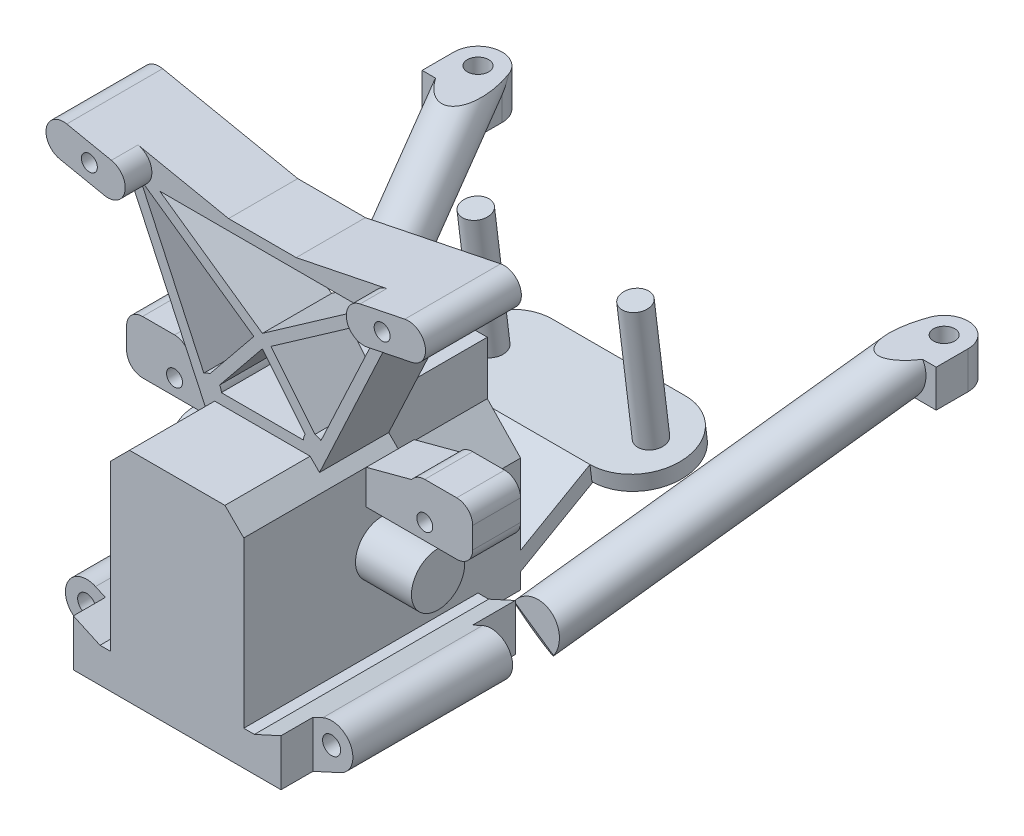
SolidWorks part; units mm, degrees
ref_plane "Front Plane" through (0, 0, 0) normal (0, 0, 1) x (1, 0, 0)
ref_plane "Top Plane" through (0, 0, 0) normal (0, 1, 0) x (1, 0, 0)
ref_plane "Right Plane" through (0, 0, 0) normal (1, 0, 0) x (0, 0, -1)
sketch "Sketch1" plane through (0, 0, 0) normal (1, 0, 0) x (0, 0, -1)
  circle A0 centre (0, 0) radius 5
  dimension "D1" = 10
extrude "Driveline Axis" add sketch "Sketch1" along normal mid plane 46 contours A0
sketch "Sketch2" plane through (0, 0, 0) normal (0, 0, 1) x (1, 0, 0)
  line L0 (-12.5, -20) -> (-12.5, 14.4645)
  line L1 (-12.5, 14.4645) -> (-8.9645, 18)
  line L2 (-8.9645, 18) -> (8.9645, 18)
  line L3 (8.9645, 18) -> (12.5, 14.4645)
  line L4 (12.5, 14.4645) -> (12.5, -20)
  line L5 (12.5, -20) -> (-12.5, -20)
  dimension "D1" = 20
  dimension "D2" = 18
  dimension "D3" = 5
  dimension "D4" = 5
  dimension "D5" = 25
  dimension "D6" = 12.5
extrude "Dummy Boss" add sketch "Sketch2" along normal mid plane 52
ref_plane "Pin Base Plane" through (0, 0, -18) normal (0, 0, -1) x (-1, 0, 0)
sketch "Sketch3" plane through (0, 0, -18) normal (0, 0, -1) x (-1, 0, 0)
  line L0 (-19.5, -23) -> (19.5, -23)
  line L1 (19.5, -23) -> (24.6641, -20.6374)
  line L2 (21.3359, -13.3626) -> (14.5, -16.49)
  line L3 (14.5, -16.49) -> (12.5, -16.49)
  line L4 (12.5, 14.4645) -> (12.5, -20) construction
  line L5 (12.5, -16.49) -> (12.5, -20)
  line L6 (12.5, -20) -> (-12.5, -20)
  line L7 (12.5, -20) -> (-12.5, -20) construction
  line L8 (0, -20) -> (0, -23) construction
  line L9 (-12.5, -16.49) -> (-12.5, -20)
  line L10 (-14.5, -16.49) -> (-12.5, -16.49)
  line L11 (-21.3359, -13.3626) -> (-14.5, -16.49)
  line L12 (-19.5, -23) -> (-24.6641, -20.6374)
  arc A0 (24.6641, -20.6374) -> (21.3359, -13.3626) centre (23, -17) ccw
  arc A1 (-24.6641, -20.6374) -> (-21.3359, -13.3626) centre (-23, -17) cw
  dimension "D3" = 4
  dimension "D1" = 17
  dimension "D2" = 23
  dimension "D4" = 3
  dimension "D5" = 2
  dimension "D6" = 7
extrude "Pin Base" add sketch "Sketch3" against normal up to surface (44 mm away) up to face at (0, 4.1548, 26)
hole_wizard "Pin Holes" positions "Sketch5" profile "Sketch7" hole size "M3" standard "ANSI Metric" end condition through all
sketch "Sketch5" plane through (0, 0, -18) normal (0, 0, -1) x (-1, 0, 0)
  arc A0 (24.6641, -20.6374) -> (21.3359, -13.3626) centre (23, -17) ccw construction
  arc A1 (-21.3359, -13.3626) -> (-24.6641, -20.6374) centre (-23, -17) ccw construction
  point P0 (-23, -17)
  point P2 (23, -17)
sketch "Sketch7" plane through (23, -17, -18) normal (1, 0, 0) x (0, 1, 0)
  line L0 (0, 0) -> (0, 44)
  line L1 (0, 44) -> (1.7, 44)
  line L2 (1.7, 44) -> (1.7, 0)
  line L5 (1.7, 0) -> (0, 0)
  line L11 (0, -6.35) -> (0, 107.95) construction
  dimension "Thru Hole Dia." = 3.4
  dimension "Thru Hole Depth" = 44
sketch "Sketch8" plane through (0, 0, 0) normal (0, 0, 1) x (1, 0, 0)
  line L0 (-10.7322, 16.2322) -> (-24.6615, 46.1036)
  line L1 (-8.9645, 18) -> (-12.5, 14.4645) construction
  line L2 (-24.6615, 46.1036) -> (-33.049, 47.8157)
  line L3 (-31.749, 54.1843) -> (-6.351, 49)
  line L4 (9.8662, 21.9942) -> (1.6121, 32.1873)
  line L5 (-6.351, 49) -> (6.351, 49)
  line L6 (0, 49) -> (0, 18) construction
  line L7 (8.9645, 18) -> (-8.9645, 18) construction
  line L8 (8.9645, 18) -> (-8.9645, 18)
  line L9 (-8.9645, 18) -> (-10.7322, 16.2322)
  line L10 (7.7145, 20) -> (-7.7145, 20)
  line L11 (-10.9977, 21.534) -> (-22.924, 47.11)
  line L12 (-8.032, 21.0813) -> (0, 31)
  line L13 (-9.8662, 21.9942) -> (-1.6121, 32.1873)
  line L14 (-1.6121, 32.1873) -> (-22.924, 47.11)
  line L15 (-19.28, 47) -> (0, 33.5)
  line L16 (8.032, 21.0813) -> (0, 31)
  line L17 (-19.28, 47) -> (19.28, 47)
  line L18 (8.9645, 18) -> (10.7322, 16.2322)
  line L19 (19.28, 47) -> (0, 33.5)
  line L20 (1.6121, 32.1873) -> (22.924, 47.11)
  line L21 (10.9977, 21.534) -> (22.924, 47.11)
  line L22 (10.7322, 16.2322) -> (24.6615, 46.1036)
  line L23 (24.6615, 46.1036) -> (33.049, 47.8157)
  line L24 (31.749, 54.1843) -> (6.351, 49)
  arc A0 (-33.049, 47.8157) -> (-31.749, 54.1843) centre (-32.399, 51) cw
  arc A1 (-7.7145, 20) -> (-8.032, 21.0813) centre (-9.7145, 20) ccw
  arc A2 (-9.8662, 21.9942) -> (-10.9977, 21.534) centre (-9.7145, 20) ccw
  circle A4 centre (-27.5, 50) radius 1.5
  arc A6 (9.8662, 21.9942) -> (10.9977, 21.534) centre (9.7145, 20) cw
  arc A7 (7.7145, 20) -> (8.032, 21.0813) centre (9.7145, 20) cw
  arc A8 (33.049, 47.8157) -> (31.749, 54.1843) centre (32.399, 51) ccw
  circle A10 centre (27.5, 50) radius 1.5
  point P32 (-5.7392, 27.0907)
  point P50 (0, 20)
  point P52 (0, 47)
  dimension "D1" = 2
  dimension "D6" = 2
  dimension "D10" = 3.25
  dimension "D11" = 55
  dimension "D12" = 29
  dimension "D13" = 3
  dimension "D2" = 2
  dimension "D3" = 2
  dimension "D4" = 2
  dimension "D5" = 2
  dimension "D7" = 0.75
  dimension "D8" = 2
  dimension "D9" = 50
  dimension "D14" = 5
  dimension "D15" = 86
  dimension "D16" = 3.25
  dimension "D17" = 64
  dimension "D18" = 11
  dimension "D19" = 51
  dimension "D20" = 33
  dimension "D24" = 2.5
extrude "Uprights" add sketch "Sketch8" along normal blind 10 and the other way blind 3 contours A2 L13 L14 L11 | L17 L6 L19 | L6 L17 L15 | L4 A6 L21 L20 | L16 L6 L10 A7 | L6 L12 A1 L10 | A4 | A10 | L22 L23 A8 L24 L5 L3 A0 L2 L0 L9 L8 L18 region at (-2.8929, 23.7148, 0) region at (2.8929, 23.7148, 0) region at (-6.4267, 42.5, 0) region at (6.4267, 42.5, 0) region at (11.7554, 33.4425, 0) region at (-11.7554, 33.4425, 0) region at (-27.5, 50, 0) region at (27.5, 50, 0)
sketch "Sketch9" plane through (0, 0, 10) normal (0, 0, 1) x (1, 0, 0)
  line L0 (-24.6615, 46.1036) -> (-33.049, 47.8157)
  line L1 (-31.749, 54.1843) -> (-23.3615, 52.4722)
  line L2 (-31.749, 54.1843) -> (-6.351, 49) construction
  line L3 (23.3615, 52.4722) -> (31.749, 54.1843)
  line L4 (31.749, 54.1843) -> (6.351, 49) construction
  line L5 (33.049, 47.8157) -> (24.6615, 46.1036)
  circle A0 centre (-27.5, 50) radius 1.5
  circle A1 centre (27.5, 50) radius 1.5
  circle A2 centre (27.5, 50) radius 1.5 construction
  circle A3 centre (-27.5, 50) radius 1.5 construction
  arc A4 (-33.049, 47.8157) -> (-31.749, 54.1843) centre (-32.399, 51) cw
  arc A5 (-31.749, 54.1843) -> (-33.049, 47.8157) centre (-32.399, 51) ccw construction
  arc A6 (-23.3615, 52.4722) -> (-24.6615, 46.1036) centre (-24.0115, 49.2879) cw
  arc A7 (31.749, 54.1843) -> (33.049, 47.8157) centre (32.399, 51) cw
  arc A8 (24.6615, 46.1036) -> (23.3615, 52.4722) centre (24.0115, 49.2879) cw
extrude "Shock Mount" add sketch "Sketch9" along normal blind 5 and the other way blind 13
sketch "Sketch10" plane through (0, 0, 0) normal (0, 0, 1) x (1, 0, 0)
  line L0 (29.5, 8) -> (12.5, 8)
  line L1 (-12.5, 14.4645) -> (-21.0556, 16.7392)
  line L2 (32.5, 11) -> (32.5, 15)
  line L3 (29.5, 18) -> (23.5, 18)
  line L4 (0, 41.2363) -> (0, 7.9844) construction
  line L5 (12.5, 8) -> (12.5, 14.4645)
  line L6 (12.5, 14.4645) -> (21.0556, 16.7392)
  line L7 (-12.5, 8) -> (-12.5, 14.4645)
  line L8 (-29.5, 18) -> (-23.5, 18)
  line L9 (-32.5, 11) -> (-32.5, 15)
  line L10 (-29.5, 8) -> (-12.5, 8)
  line L11 (12.5, -16.49) -> (12.5, 14.4645) construction
  arc A0 (29.5, 8) -> (32.5, 11) centre (29.5, 11) ccw
  circle A1 centre (23.5, 11) radius 1.5
  arc A2 (21.0556, 16.7392) -> (23.5, 18) centre (23.5, 15) cw
  arc A3 (29.5, 18) -> (32.5, 15) centre (29.5, 15) cw
  arc A4 (-29.5, 18) -> (-32.5, 15) centre (-29.5, 15) ccw
  arc A5 (-21.0556, 16.7392) -> (-23.5, 18) centre (-23.5, 15) ccw
  circle A6 centre (-23.5, 11) radius 1.5
  arc A7 (-29.5, 8) -> (-32.5, 11) centre (-29.5, 11) cw
  point P11 (0, 0)
  point P23 (0, 0)
  point P29 (19.8778, 11)
  point P30 (19.5782, 17.8112)
  point P31 (13.1169, 7.9844)
  point P32 (19.2867, 14.2865)
  point P35 (0, 0)
  point P36 (0, 0)
  dimension "D1" = 3
  dimension "D2" = 3
  dimension "D3" = 3
  dimension "D4" = 4
  dimension "D6" = 3
  dimension "D5" = 6
  dimension "D7" = 47
  dimension "D10" = 11
extrude "Turnbuckle Mounts" add sketch "Sketch10" against normal blind 6 and the other way blind 3
sketch "Sketch11" plane through (0, 0, -26) normal (0, 0, -1) x (-1, 0, 0)
  line L0 (-12.5, 1.4645) -> (-6.25, 8)
  line L1 (-12.5, -20) -> (-12.5, 14.4645) construction
  line L2 (-6.25, 8) -> (-6.25, 18)
  line L3 (-8.9645, 18) -> (8.9645, 18) construction
  line L4 (5.75, 18) -> (8.9645, 18)
  line L5 (-8.9645, 18) -> (8.9645, 18) construction
  line L6 (5.75, 18) -> (5.75, 8)
  line L7 (5.75, 8) -> (12.5, 1.5449)
  line L8 (12.5, 14.4645) -> (12.5, -20) construction
  line L9 (-12.5, 1.4645) -> (-12.5, 14.4645)
  line L10 (-6.25, 18) -> (-8.9645, 18)
  line L11 (8.9645, 18) -> (12.5, 14.4645)
  line L13 (8.9645, 18) -> (10.7322, 16.2322) construction
  line L14 (12.5, 14.4645) -> (12.5, 1.5449)
  line L15 (12.5, 1.5449) -> (12.5075, 1.5371)
  line L16 (-8.9645, 18) -> (-12.5, 14.4645)
  line L17 (-12.5, 14.4645) -> (-12.5234, 14.4847)
  line L18 (-12.5, 14.4645) -> (-8.9645, 18) construction
  point P14 (-12.5, 14.4645)
  line M5 (12.5, -20) -> (12.5, 14.4645)
  line M6 (12.5, 14.4645) -> (8.9645, 18)
  line M7 (8.9645, 18) -> (-8.9645, 18)
  line M8 (-8.9645, 18) -> (-12.5, 14.4645)
  line M9 (-12.5, 14.4645) -> (-12.5, -20)
  dimension "D1" = 12
  dimension "D2" = 10
  dimension "D3" = 6.25
extrude "Turnbuckle Room" cut sketch "Sketch11" against normal blind 23 and the other way through all contours L6 L7 M5 M6 M7 | L0 L2 M7 M8 M9 region at (9.4938, 10.7764, -26) region at (-9.2548, 10.836, -26)
ref_point "Reference Points 1"
ref_point "Reference Point 2"
ref_plane "Plane for Reference sketch" through (0, -17, 0) normal (0, -1, 0) x (-1, 0, 0)
sketch "Reference Sketch" plane through (0, -17, 0) normal (0, -1, 0) x (-1, 0, 0)
  line L0 (-23, -26) -> (-23, 53.7255) construction
  line L1 (-23, 18) -> (-47, 83)
  line L2 (-24.6641, 18) -> (-19.5, 18) construction
  line L3 (-47, 83) -> (-9.0462, 83) construction
  line L4 (-19.5, 18) -> (19.5, 18) construction
  line L5 (-47, 92.1966) -> (-47, -9.4225) construction
  dimension "D1" = 65
  dimension "D2" = 24
ref_axis "Axis3" through (23, -7.1107, -18) along (0, -1, 0)
ref_plane "Plane For Chassis Arm" through (14.3918, 0, 5.3139) normal (0.9381, 0, 0.3464) x (0.3464, 0, -0.9381)
sketch "Sketch13" plane through (14.3918, 0, 5.3139) normal (0.9381, 0, 0.3464) x (0.3464, 0, -0.9381)
  line L0 (24.8523, -17) -> (84.8523, 13) construction
  line L1 (102.7689, -17) -> (7.4404, -17) construction
  line L2 (24.8523, -7.1107) -> (24.8523, -34.5046) construction
  line L3 (24.8523, -17) -> (84.8523, 13)
  dimension "D1" = 30
  dimension "D2" = 60
sweep "Arm" add path "Sketch13" circular profile diameter 9 parameters "D3"=9
mirror "Mirror1" about plane through (0, 0, 0) normal (1, 0, 0) of "Arm"
ref_point "Point4"
ref_plane "Plane4" through (0, 13, 0) normal (0, -1, 0) x (-1, 0, 0)
sketch "Sketch28" plane through (0, 13, 0) normal (0, -1, 0) x (-1, 0, 0)
  line L2 (-39.2824, 74.2858) -> (-39.2824, 68.2858)
  line L3 (-39.2824, 68.2858) -> (-48.2824, 68.2858)
  line L4 (-48.2824, 74.2858) -> (-48.2824, 68.2858)
  arc A0 (-39.2824, 74.2858) -> (-48.2824, 74.2858) centre (-43.7824, 74.2858) ccw
  point P5 (-43.7824, 68.2858)
  dimension "D1" = 4.5
  dimension "D2" = 6
extrude "Chassis mount" add sketch "Sketch28" along normal blind 7
mirror "Mirror2" about plane through (0, 0, 0) normal (1, 0, 0) of "Chassis mount"
sketch "Sketch29" plane through (0, 0, 0) normal (1, 0, 0) x (0, 0, -1)
  line L1 (78.7858, 13) -> (60.9188, 13)
  line L2 (78.7858, 13) -> (78.7858, 18.3401)
  line L3 (78.7858, 18.3401) -> (60.9188, 18.3401)
  line L4 (60.9188, 13) -> (60.9188, 18.3401)
extrude "Trim" cut sketch "Sketch29" against normal mid plane 100
sketch "Sketch30" plane through (0, 13, 0) normal (0, -1, 0) x (-1, 0, 0)
  circle A0 centre (-43.7824, 74.2858) radius 2
  dimension "D1" = 4
extrude "Chassis Holes" cut sketch "Sketch30" along normal up to surface (7 mm away) up to face at (43.9693, 6, -72.1984)
mirror "Mirror3" about plane through (0, 0, 0) normal (1, 0, 0) of "Chassis Holes"
sketch "Sketch40" plane through (0, 0, 0) normal (1, 0, 0) x (0, 0, -1)
  line L0 (26, -13.5453) -> (39.0359, -6.1007)
  line L1 (26, -20) -> (26, 1.4645) construction
  line L2 (26, -17) -> (40, -9.0048)
  line L5 (39.0359, -6.1007) -> (56.9641, -3.8993)
  line L6 (56.9641, -3.8993) -> (56.9641, -6.9219)
  line L7 (56.9641, -6.9219) -> (40, -9.0048)
  line L8 (26, -13.5453) -> (26, -17)
  line L9 (48, -5) -> (48, -8.0225) construction
  line L10 (26, -20) -> (58.296, -20) construction
  line L11 (-26, 4.7618) -> (-26, -8.0225) construction
  line L12 (-26, -16.49) -> (-26, 14.4645) construction
  point P15 (32.5179, -9.823)
  dimension "D1" = 3
  dimension "D2" = 3
  dimension "D3" = 74
  dimension "D4" = 7
  dimension "D5" = 15
  dimension "D6" = 3
  dimension "D7" = 14
extrude "Boss-Extrude2" add sketch "Sketch40" along normal mid plane 25
sketch "Sketch41" plane through (0, -10.7319, -1.3177) normal (0, 0.9925, 0.1219) x (1, 0, 0)
  line L0 (12.5, 56.0643) -> (12.5, 38.0014) construction
  line L1 (12.5, 56.0643) -> (12.5, 38.0014)
  arc A0 (12.5, 38.0014) -> (12.5, 56.0643) centre (12.5, 47.0329) ccw
extrude "Boss-Extrude3" add sketch "Sketch41" against normal up to surface (3 mm away) up to face at (0, -7.9633, -48.4821)
mirror "Mirror4" about plane through (0, 0, 0) normal (1, 0, 0) of "Boss-Extrude3"
sketch "Sketch43" plane through (0, -10.7319, -1.3177) normal (0, 0.9925, 0.1219) x (1, 0, 0)
  line L0 (-21.5314, 47.0329) -> (21.5314, 47.0329) construction
  line L1 (0, 61.4593) -> (0, 50.7815) construction
  arc A0 (-12.5, 56.0643) -> (-12.5, 38.0014) centre (-12.5, 47.0329) ccw construction
  arc A1 (12.5, 38.0014) -> (12.5, 56.0643) centre (12.5, 47.0329) ccw construction
  circle A2 centre (-15, 47.0329) radius 2.5
  circle A3 centre (15, 47.0329) radius 2.5
  dimension "D1" = 5
  dimension "D2" = 5
  dimension "D3" = 30
  dimension "D4" = 15
extrude "Boss-Extrude4" add sketch "Sketch43" along normal blind 24
sketch "Sketch45" plane through (0, -23, 0) normal (0, -1, 0) x (1, 0, 0)
  line L0 (19.5, 26) -> (19.5, -18) construction
  line L1 (19.5, -18) -> (30.4887, -18)
  line L2 (19.5, -18) -> (19.5, -10)
  line L3 (19.5, -10) -> (30.4887, -10)
  line L4 (30.4887, -18) -> (30.4887, -10)
  line L5 (19.5, 20) -> (30.4887, 20)
  line L6 (19.5, 20) -> (19.5, 28)
  line L7 (19.5, 28) -> (30.4887, 28)
  line L8 (30.4887, 20) -> (30.4887, 28)
  line L9 (0, 0) -> (0, 34.8811) construction
  line L10 (-30.4887, 20) -> (-30.4887, 28)
  line L11 (-19.5, 28) -> (-30.4887, 28)
  line L12 (-19.5, 20) -> (-19.5, 28)
  line L13 (-19.5, 20) -> (-30.4887, 20)
  line L14 (-30.4887, -18) -> (-30.4887, -10)
  line L15 (-19.5, -10) -> (-30.4887, -10)
  line L16 (-19.5, -18) -> (-19.5, -10)
  line L17 (-19.5, -18) -> (-30.4887, -18)
  dimension "D1" = 8
  dimension "D2" = 8
  dimension "D3" = 30
extrude "Cut-Extrude5" cut sketch "Sketch45" against normal blind 14
